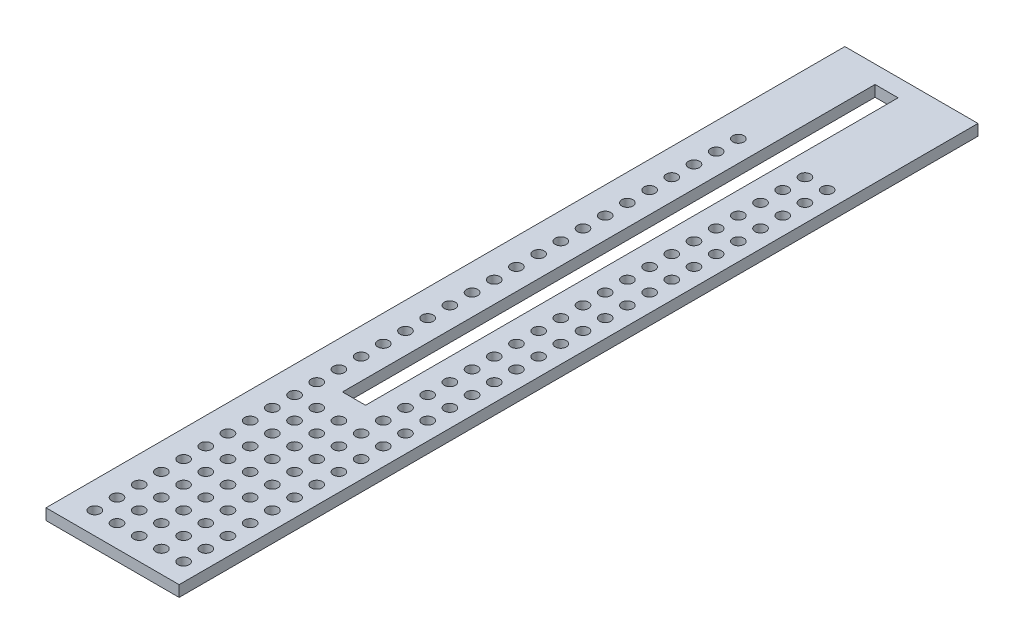
SolidWorks part; units mm, degrees
ref_plane "Front Plane" through (0, 0, 0) normal (0, 0, 1) x (1, 0, 0)
ref_plane "Top Plane" through (0, 0, 0) normal (0, 1, 0) x (1, 0, 0)
ref_plane "Right Plane" through (0, 0, 0) normal (1, 0, 0) x (0, 0, -1)
sketch "Sketch1" plane through (0, 0, 0) normal (0, 0, 1) x (1, 0, 0)
  line L0 (1.5875, 47.625) -> (36.5125, 47.625)
  line L1 (1.5875, -50.8) -> (-1.5875, -50.8)
  line L2 (1.5875, -50.8) -> (1.5875, 47.625)
  line L4 (-1.5875, -50.8) -> (-1.5875, 50.8)
  line L5 (1.5875, -50.8) -> (-1.5875, 50.8) construction
  line L6 (3.5127, 112.4075) -> (-1.5875, -50.8) construction
  line L7 (-1.5875, 50.8) -> (36.5125, 50.8)
  line L10 (36.5125, 50.8) -> (36.5125, 47.625)
  point P0 (0, 0)
  point P7 (0, -50.8)
  dimension "D1" = 3.175
  dimension "D2" = 3.175
  dimension "D3" = 38.1
  dimension "D4" = 101.6
extrude "Boss-Extrude1" add sketch "Sketch1" along normal blind 228.6
sketch "Sketch2" plane through (1.5875, 0, 0) normal (1, 0, 0) x (0, 0, -1)
  line L0 (-228.6, -29.4596) -> (0, 47.625) construction
  line L1 (-228.6, -50.8) -> (-228.6, 47.625) construction
  line L2 (-228.6, 47.625) -> (0, 47.625) construction
  line L3 (0, -50.8) -> (0, 47.625) construction
ref_plane "Plane1 - BACKBOARD PLANE" through (0, 42.7626, 14.4197) normal (0, -0.9476, -0.3195) x (0, 0.3195, -0.9476)
ref_plane "Plane1" through (0, -1.5875, 0) normal (0, -1, 0) x (-1, 0, 0)
sketch "Sketch3" plane through (-1.5875, 0, 0) normal (-1, 0, 0) x (0, 0, 1)
  line L0 (228.6, -50.8) -> (0, -50.8) construction
  line L1 (82.55, -32.385) -> (6.35, -32.385)
  line L2 (82.55, -32.385) -> (82.55, -38.735)
  line L3 (82.55, -38.735) -> (6.35, -38.735)
  line L4 (6.35, -32.385) -> (6.35, -38.735)
  line L5 (82.55, -32.385) -> (6.35, -38.735) construction
  line L6 (82.55, -38.735) -> (6.35, -32.385) construction
  line L7 (0, 50.8) -> (0, -50.8) construction
  line L18 (6.35, 33.1888) -> (82.55, 33.1888)
  line L19 (6.35, 33.1888) -> (6.35, 26.2472)
  line L20 (6.35, 26.2472) -> (82.55, 26.2472)
  line L21 (82.55, 33.1888) -> (82.55, 26.2472)
  point P0 (44.45, -35.56)
  point P13 (6.35, 29.718)
  point P14 (6.35, -35.56)
  dimension "D1" = 6.35
  dimension "D2" = 15.24
  dimension "D3" = 76.2
  dimension "D4" = 6.35
  dimension "D5" = 65.278
extrude "Cut-Extrude1" cut sketch "Sketch3" against normal up to next
sketch "Sketch4" plane through (-1.5875, 0, 0) normal (-1, 0, 0) x (0, 0, 1)
  circle A0 centre (103.8185, 40.3289) radius 1.5875
  circle A1 centre (110.1685, 40.3289) radius 1.5875
  circle A2 centre (116.5185, 40.3289) radius 1.5875
  circle A3 centre (122.8685, 40.3289) radius 1.5875
  circle A4 centre (129.2185, 40.3289) radius 1.5875
  circle A5 centre (110.1685, 33.9789) radius 1.5875
  circle A6 centre (116.5185, 33.9789) radius 1.5875
  circle A7 centre (122.8685, 33.9789) radius 1.5875
  circle A8 centre (129.2185, 33.9789) radius 1.5875
  circle A9 centre (110.1685, 27.6289) radius 1.5875
  circle A10 centre (116.5185, 27.6289) radius 1.5875
  circle A11 centre (122.8685, 27.6289) radius 1.5875
  circle A12 centre (129.2185, 27.6289) radius 1.5875
  circle A13 centre (110.1685, 21.2789) radius 1.5875
  circle A14 centre (116.5185, 21.2789) radius 1.5875
  circle A15 centre (122.8685, 21.2789) radius 1.5875
  circle A16 centre (129.2185, 21.2789) radius 1.5875
  circle A17 centre (103.8185, 33.9789) radius 1.5875
  circle A18 centre (103.8185, 27.6289) radius 1.5875
  circle A19 centre (103.8185, 21.2789) radius 1.5875
  circle A20 centre (135.5685, 40.3289) radius 1.5875
  circle A21 centre (141.9185, 40.3289) radius 1.5875
  circle A22 centre (148.2685, 40.3289) radius 1.5875
  circle A23 centre (154.6185, 40.3289) radius 1.5875
  circle A24 centre (160.9685, 40.3289) radius 1.5875
  circle A25 centre (167.3185, 40.3289) radius 1.5875
  circle A26 centre (173.6685, 40.3289) radius 1.5875
  circle A27 centre (180.0185, 40.3289) radius 1.5875
  circle A28 centre (186.3685, 40.3289) radius 1.5875
  circle A29 centre (192.7185, 40.3289) radius 1.5875
  circle A30 centre (199.0685, 40.3289) radius 1.5875
  circle A31 centre (205.4185, 40.3289) radius 1.5875
  circle A32 centre (211.7685, 40.3289) radius 1.5875
  circle A33 centre (218.1185, 40.3289) radius 1.5875
  circle A34 centre (135.5685, 33.9789) radius 1.5875
  circle A35 centre (141.9185, 33.9789) radius 1.5875
  circle A36 centre (148.2685, 33.9789) radius 1.5875
  circle A37 centre (154.6185, 33.9789) radius 1.5875
  circle A38 centre (160.9685, 33.9789) radius 1.5875
  circle A39 centre (167.3185, 33.9789) radius 1.5875
  circle A40 centre (173.6685, 33.9789) radius 1.5875
  circle A41 centre (180.0185, 33.9789) radius 1.5875
  circle A42 centre (186.3685, 33.9789) radius 1.5875
  circle A43 centre (192.7185, 33.9789) radius 1.5875
  circle A44 centre (199.0685, 33.9789) radius 1.5875
  circle A45 centre (205.4185, 33.9789) radius 1.5875
  circle A46 centre (211.7685, 33.9789) radius 1.5875
  circle A47 centre (218.1185, 33.9789) radius 1.5875
  circle A48 centre (135.5685, 27.6289) radius 1.5875
  circle A49 centre (141.9185, 27.6289) radius 1.5875
  circle A50 centre (148.2685, 27.6289) radius 1.5875
  circle A51 centre (154.6185, 27.6289) radius 1.5875
  circle A52 centre (160.9685, 27.6289) radius 1.5875
  circle A53 centre (167.3185, 27.6289) radius 1.5875
  circle A54 centre (173.6685, 27.6289) radius 1.5875
  circle A55 centre (180.0185, 27.6289) radius 1.5875
  circle A56 centre (186.3685, 27.6289) radius 1.5875
  circle A57 centre (192.7185, 27.6289) radius 1.5875
  circle A58 centre (199.0685, 27.6289) radius 1.5875
  circle A59 centre (205.4185, 27.6289) radius 1.5875
  circle A60 centre (211.7685, 27.6289) radius 1.5875
  circle A61 centre (218.1185, 27.6289) radius 1.5875
  circle A62 centre (135.5685, 21.2789) radius 1.5875
  circle A63 centre (141.9185, 21.2789) radius 1.5875
  circle A64 centre (148.2685, 21.2789) radius 1.5875
  circle A65 centre (154.6185, 21.2789) radius 1.5875
  circle A66 centre (160.9685, 21.2789) radius 1.5875
  circle A67 centre (167.3185, 21.2789) radius 1.5875
  circle A68 centre (173.6685, 21.2789) radius 1.5875
  circle A69 centre (180.0185, 21.2789) radius 1.5875
  circle A70 centre (186.3685, 21.2789) radius 1.5875
  circle A71 centre (192.7185, 21.2789) radius 1.5875
  circle A72 centre (199.0685, 21.2789) radius 1.5875
  circle A73 centre (205.4185, 21.2789) radius 1.5875
  circle A74 centre (211.7685, 21.2789) radius 1.5875
  circle A75 centre (218.1185, 21.2789) radius 1.5875
  circle A76 centre (103.8185, 14.9289) radius 1.5875
  circle A77 centre (110.1685, 14.9289) radius 1.5875
  circle A78 centre (116.5185, 14.9289) radius 1.5875
  circle A79 centre (122.8685, 14.9289) radius 1.5875
  circle A80 centre (129.2185, 14.9289) radius 1.5875
  circle A81 centre (135.5685, 14.9289) radius 1.5875
  circle A82 centre (141.9185, 14.9289) radius 1.5875
  circle A83 centre (148.2685, 14.9289) radius 1.5875
  circle A84 centre (154.6185, 14.9289) radius 1.5875
  circle A85 centre (160.9685, 14.9289) radius 1.5875
  circle A86 centre (167.3185, 14.9289) radius 1.5875
  circle A87 centre (173.6685, 14.9289) radius 1.5875
  circle A88 centre (180.0185, 14.9289) radius 1.5875
  circle A89 centre (186.3685, 14.9289) radius 1.5875
  circle A90 centre (192.7185, 14.9289) radius 1.5875
  circle A91 centre (199.0685, 14.9289) radius 1.5875
  circle A92 centre (205.4185, 14.9289) radius 1.5875
  circle A93 centre (211.7685, 14.9289) radius 1.5875
  circle A94 centre (218.1185, 14.9289) radius 1.5875
  circle A95 centre (103.8185, 8.5789) radius 1.5875
  circle A96 centre (110.1685, 8.5789) radius 1.5875
  circle A97 centre (116.5185, 8.5789) radius 1.5875
  circle A98 centre (122.8685, 8.5789) radius 1.5875
  circle A99 centre (129.2185, 8.5789) radius 1.5875
  circle A100 centre (135.5685, 8.5789) radius 1.5875
  circle A101 centre (141.9185, 8.5789) radius 1.5875
  circle A102 centre (148.2685, 8.5789) radius 1.5875
  circle A103 centre (154.6185, 8.5789) radius 1.5875
  circle A104 centre (160.9685, 8.5789) radius 1.5875
  circle A105 centre (167.3185, 8.5789) radius 1.5875
  circle A106 centre (173.6685, 8.5789) radius 1.5875
  circle A107 centre (180.0185, 8.5789) radius 1.5875
  circle A108 centre (186.3685, 8.5789) radius 1.5875
  circle A109 centre (192.7185, 8.5789) radius 1.5875
  circle A110 centre (199.0685, 8.5789) radius 1.5875
  circle A111 centre (205.4185, 8.5789) radius 1.5875
  circle A112 centre (211.7685, 8.5789) radius 1.5875
  circle A113 centre (218.1185, 8.5789) radius 1.5875
  circle A114 centre (103.8185, 2.2289) radius 1.5875
  circle A115 centre (110.1685, 2.2289) radius 1.5875
  circle A116 centre (116.5185, 2.2289) radius 1.5875
  circle A117 centre (122.8685, 2.2289) radius 1.5875
  circle A118 centre (129.2185, 2.2289) radius 1.5875
  circle A119 centre (135.5685, 2.2289) radius 1.5875
  circle A120 centre (141.9185, 2.2289) radius 1.5875
  circle A121 centre (148.2685, 2.2289) radius 1.5875
  circle A122 centre (154.6185, 2.2289) radius 1.5875
  circle A123 centre (160.9685, 2.2289) radius 1.5875
  circle A124 centre (167.3185, 2.2289) radius 1.5875
  circle A125 centre (173.6685, 2.2289) radius 1.5875
  circle A126 centre (180.0185, 2.2289) radius 1.5875
  circle A127 centre (186.3685, 2.2289) radius 1.5875
  circle A128 centre (192.7185, 2.2289) radius 1.5875
  circle A129 centre (199.0685, 2.2289) radius 1.5875
  circle A130 centre (205.4185, 2.2289) radius 1.5875
  circle A131 centre (211.7685, 2.2289) radius 1.5875
  circle A132 centre (218.1185, 2.2289) radius 1.5875
  circle A133 centre (103.8185, -4.1211) radius 1.5875
  circle A134 centre (110.1685, -4.1211) radius 1.5875
  circle A135 centre (116.5185, -4.1211) radius 1.5875
  circle A136 centre (122.8685, -4.1211) radius 1.5875
  circle A137 centre (129.2185, -4.1211) radius 1.5875
  circle A138 centre (135.5685, -4.1211) radius 1.5875
  circle A139 centre (141.9185, -4.1211) radius 1.5875
  circle A140 centre (148.2685, -4.1211) radius 1.5875
  circle A141 centre (154.6185, -4.1211) radius 1.5875
  circle A142 centre (160.9685, -4.1211) radius 1.5875
  circle A143 centre (167.3185, -4.1211) radius 1.5875
  circle A144 centre (173.6685, -4.1211) radius 1.5875
  circle A145 centre (180.0185, -4.1211) radius 1.5875
  circle A146 centre (186.3685, -4.1211) radius 1.5875
  circle A147 centre (192.7185, -4.1211) radius 1.5875
  circle A148 centre (199.0685, -4.1211) radius 1.5875
  circle A149 centre (205.4185, -4.1211) radius 1.5875
  circle A150 centre (211.7685, -4.1211) radius 1.5875
  circle A151 centre (218.1185, -4.1211) radius 1.5875
  circle A152 centre (103.8185, -10.4711) radius 1.5875
  circle A153 centre (110.1685, -10.4711) radius 1.5875
  circle A154 centre (116.5185, -10.4711) radius 1.5875
  circle A155 centre (122.8685, -10.4711) radius 1.5875
  circle A156 centre (129.2185, -10.4711) radius 1.5875
  circle A157 centre (135.5685, -10.4711) radius 1.5875
  circle A158 centre (141.9185, -10.4711) radius 1.5875
  circle A159 centre (148.2685, -10.4711) radius 1.5875
  circle A160 centre (154.6185, -10.4711) radius 1.5875
  circle A161 centre (160.9685, -10.4711) radius 1.5875
  circle A162 centre (167.3185, -10.4711) radius 1.5875
  circle A163 centre (173.6685, -10.4711) radius 1.5875
  circle A164 centre (180.0185, -10.4711) radius 1.5875
  circle A165 centre (186.3685, -10.4711) radius 1.5875
  circle A166 centre (192.7185, -10.4711) radius 1.5875
  circle A167 centre (199.0685, -10.4711) radius 1.5875
  circle A168 centre (205.4185, -10.4711) radius 1.5875
  circle A169 centre (211.7685, -10.4711) radius 1.5875
  circle A170 centre (218.1185, -10.4711) radius 1.5875
  circle A171 centre (103.8185, -16.8211) radius 1.5875
  circle A172 centre (110.1685, -16.8211) radius 1.5875
  circle A173 centre (116.5185, -16.8211) radius 1.5875
  circle A174 centre (122.8685, -16.8211) radius 1.5875
  circle A175 centre (129.2185, -16.8211) radius 1.5875
  circle A176 centre (135.5685, -16.8211) radius 1.5875
  circle A177 centre (141.9185, -16.8211) radius 1.5875
  circle A178 centre (148.2685, -16.8211) radius 1.5875
  circle A179 centre (154.6185, -16.8211) radius 1.5875
  circle A180 centre (160.9685, -16.8211) radius 1.5875
  circle A181 centre (167.3185, -16.8211) radius 1.5875
  circle A182 centre (173.6685, -16.8211) radius 1.5875
  circle A183 centre (180.0185, -16.8211) radius 1.5875
  circle A184 centre (186.3685, -16.8211) radius 1.5875
  circle A185 centre (192.7185, -16.8211) radius 1.5875
  circle A186 centre (199.0685, -16.8211) radius 1.5875
  circle A187 centre (205.4185, -16.8211) radius 1.5875
  circle A188 centre (211.7685, -16.8211) radius 1.5875
  circle A189 centre (218.1185, -16.8211) radius 1.5875
  circle A190 centre (103.8185, -23.1711) radius 1.5875
  circle A191 centre (110.1685, -23.1711) radius 1.5875
  circle A192 centre (116.5185, -23.1711) radius 1.5875
  circle A193 centre (122.8685, -23.1711) radius 1.5875
  circle A194 centre (129.2185, -23.1711) radius 1.5875
  circle A195 centre (135.5685, -23.1711) radius 1.5875
  circle A196 centre (141.9185, -23.1711) radius 1.5875
  circle A197 centre (148.2685, -23.1711) radius 1.5875
  circle A198 centre (154.6185, -23.1711) radius 1.5875
  circle A199 centre (160.9685, -23.1711) radius 1.5875
  circle A200 centre (167.3185, -23.1711) radius 1.5875
  circle A201 centre (173.6685, -23.1711) radius 1.5875
  circle A202 centre (180.0185, -23.1711) radius 1.5875
  circle A203 centre (186.3685, -23.1711) radius 1.5875
  circle A204 centre (192.7185, -23.1711) radius 1.5875
  circle A205 centre (199.0685, -23.1711) radius 1.5875
  circle A206 centre (205.4185, -23.1711) radius 1.5875
  circle A207 centre (211.7685, -23.1711) radius 1.5875
  circle A208 centre (218.1185, -23.1711) radius 1.5875
  circle A209 centre (103.8185, -29.5211) radius 1.5875
  circle A210 centre (110.1685, -29.5211) radius 1.5875
  circle A211 centre (116.5185, -29.5211) radius 1.5875
  circle A212 centre (122.8685, -29.5211) radius 1.5875
  circle A213 centre (129.2185, -29.5211) radius 1.5875
  circle A214 centre (135.5685, -29.5211) radius 1.5875
  circle A215 centre (141.9185, -29.5211) radius 1.5875
  circle A216 centre (148.2685, -29.5211) radius 1.5875
  circle A217 centre (154.6185, -29.5211) radius 1.5875
  circle A218 centre (160.9685, -29.5211) radius 1.5875
  circle A219 centre (167.3185, -29.5211) radius 1.5875
  circle A220 centre (173.6685, -29.5211) radius 1.5875
  circle A221 centre (180.0185, -29.5211) radius 1.5875
  circle A222 centre (186.3685, -29.5211) radius 1.5875
  circle A223 centre (192.7185, -29.5211) radius 1.5875
  circle A224 centre (199.0685, -29.5211) radius 1.5875
  circle A225 centre (205.4185, -29.5211) radius 1.5875
  circle A226 centre (211.7685, -29.5211) radius 1.5875
  circle A227 centre (218.1185, -29.5211) radius 1.5875
  circle A228 centre (103.8185, -35.8711) radius 1.5875
  circle A229 centre (110.1685, -35.8711) radius 1.5875
  circle A230 centre (116.5185, -35.8711) radius 1.5875
  circle A231 centre (122.8685, -35.8711) radius 1.5875
  circle A232 centre (129.2185, -35.8711) radius 1.5875
  circle A233 centre (135.5685, -35.8711) radius 1.5875
  circle A234 centre (141.9185, -35.8711) radius 1.5875
  circle A235 centre (148.2685, -35.8711) radius 1.5875
  circle A236 centre (154.6185, -35.8711) radius 1.5875
  circle A237 centre (160.9685, -35.8711) radius 1.5875
  circle A238 centre (167.3185, -35.8711) radius 1.5875
  circle A239 centre (173.6685, -35.8711) radius 1.5875
  circle A240 centre (180.0185, -35.8711) radius 1.5875
  circle A241 centre (186.3685, -35.8711) radius 1.5875
  circle A242 centre (192.7185, -35.8711) radius 1.5875
  circle A243 centre (199.0685, -35.8711) radius 1.5875
  circle A244 centre (205.4185, -35.8711) radius 1.5875
  circle A245 centre (211.7685, -35.8711) radius 1.5875
  circle A246 centre (218.1185, -35.8711) radius 1.5875
  circle A247 centre (103.8185, -42.2211) radius 1.5875
  circle A248 centre (110.1685, -42.2211) radius 1.5875
  circle A249 centre (116.5185, -42.2211) radius 1.5875
  circle A250 centre (122.8685, -42.2211) radius 1.5875
  circle A251 centre (129.2185, -42.2211) radius 1.5875
  circle A252 centre (135.5685, -42.2211) radius 1.5875
  circle A253 centre (141.9185, -42.2211) radius 1.5875
  circle A254 centre (148.2685, -42.2211) radius 1.5875
  circle A255 centre (154.6185, -42.2211) radius 1.5875
  circle A256 centre (160.9685, -42.2211) radius 1.5875
  circle A257 centre (167.3185, -42.2211) radius 1.5875
  circle A258 centre (173.6685, -42.2211) radius 1.5875
  circle A259 centre (180.0185, -42.2211) radius 1.5875
  circle A260 centre (186.3685, -42.2211) radius 1.5875
  circle A261 centre (192.7185, -42.2211) radius 1.5875
  circle A262 centre (199.0685, -42.2211) radius 1.5875
  circle A263 centre (205.4185, -42.2211) radius 1.5875
  circle A264 centre (211.7685, -42.2211) radius 1.5875
  circle A265 centre (218.1185, -42.2211) radius 1.5875
  dimension "D1" = 3.175
  dimension "D2" = 19
  dimension "D3" = 14
extrude "Cut-Extrude2" cut sketch "Sketch4" against normal up to next (3.175 mm away)
sketch "Sketch5" plane through (0, 50.8, 0) normal (0, 1, 0) x (1, 0, 0)
  line L0 (36.5125, 0) -> (-1.5875, 0) construction
  line L1 (18.7325, -5.08) -> (12.1285, -5.08)
  line L2 (18.7325, -5.08) -> (18.7325, -157.48)
  line L3 (18.7325, -157.48) -> (12.1285, -157.48)
  line L4 (12.1285, -5.08) -> (12.1285, -157.48)
  line L5 (36.5125, -228.6) -> (36.5125, 0) construction
  point P8 (15.4305, -5.08)
  dimension "D1" = 6.604
  dimension "D2" = 152.4
  dimension "D3" = 5.08
  dimension "D4" = 21.082
extrude "Cut-Extrude3" cut sketch "Sketch5" against normal up to next
sketch "Sketch6" plane through (0, 50.8, 0) normal (0, 1, 0) x (1, 0, 0)
  line L0 (36.5125, -228.6) -> (-1.5875, -228.6) construction
  line L1 (36.5125, -228.6) -> (36.5125, 0) construction
  circle A0 centre (6.0325, -222.25) radius 1.5875
  circle A1 centre (12.3825, -222.25) radius 1.5875
  circle A2 centre (18.7325, -222.25) radius 1.5875
  circle A3 centre (25.0825, -222.25) radius 1.5875
  circle A4 centre (31.4325, -222.25) radius 1.5875
  circle A5 centre (12.3825, -215.9) radius 1.5875
  circle A6 centre (18.7325, -215.9) radius 1.5875
  circle A7 centre (25.0825, -215.9) radius 1.5875
  circle A8 centre (31.4325, -215.9) radius 1.5875
  circle A9 centre (12.3825, -209.55) radius 1.5875
  circle A10 centre (18.7325, -209.55) radius 1.5875
  circle A11 centre (25.0825, -209.55) radius 1.5875
  circle A12 centre (31.4325, -209.55) radius 1.5875
  circle A13 centre (12.3825, -203.2) radius 1.5875
  circle A14 centre (18.7325, -203.2) radius 1.5875
  circle A15 centre (25.0825, -203.2) radius 1.5875
  circle A16 centre (31.4325, -203.2) radius 1.5875
  circle A17 centre (12.3825, -196.85) radius 1.5875
  circle A18 centre (18.7325, -196.85) radius 1.5875
  circle A19 centre (25.0825, -196.85) radius 1.5875
  circle A20 centre (31.4325, -196.85) radius 1.5875
  circle A21 centre (12.3825, -190.5) radius 1.5875
  circle A22 centre (18.7325, -190.5) radius 1.5875
  circle A23 centre (25.0825, -190.5) radius 1.5875
  circle A24 centre (31.4325, -190.5) radius 1.5875
  circle A25 centre (12.3825, -184.15) radius 1.5875
  circle A26 centre (18.7325, -184.15) radius 1.5875
  circle A27 centre (25.0825, -184.15) radius 1.5875
  circle A28 centre (31.4325, -184.15) radius 1.5875
  circle A29 centre (12.3825, -177.8) radius 1.5875
  circle A30 centre (18.7325, -177.8) radius 1.5875
  circle A31 centre (25.0825, -177.8) radius 1.5875
  circle A32 centre (31.4325, -177.8) radius 1.5875
  circle A33 centre (12.3825, -171.45) radius 1.5875
  circle A34 centre (18.7325, -171.45) radius 1.5875
  circle A35 centre (25.0825, -171.45) radius 1.5875
  circle A36 centre (31.4325, -171.45) radius 1.5875
  circle A37 centre (12.3825, -165.1) radius 1.5875
  circle A38 centre (18.7325, -165.1) radius 1.5875
  circle A39 centre (25.0825, -165.1) radius 1.5875
  circle A40 centre (31.4325, -165.1) radius 1.5875
  circle A43 centre (25.0825, -158.75) radius 1.5875
  circle A44 centre (31.4325, -158.75) radius 1.5875
  circle A47 centre (25.0825, -152.4) radius 1.5875
  circle A48 centre (31.4325, -152.4) radius 1.5875
  circle A51 centre (25.0825, -146.05) radius 1.5875
  circle A52 centre (31.4325, -146.05) radius 1.5875
  circle A55 centre (25.0825, -139.7) radius 1.5875
  circle A56 centre (31.4325, -139.7) radius 1.5875
  circle A59 centre (25.0825, -133.35) radius 1.5875
  circle A60 centre (31.4325, -133.35) radius 1.5875
  circle A63 centre (25.0825, -127) radius 1.5875
  circle A64 centre (31.4325, -127) radius 1.5875
  circle A67 centre (25.0825, -120.65) radius 1.5875
  circle A68 centre (31.4325, -120.65) radius 1.5875
  circle A71 centre (25.0825, -114.3) radius 1.5875
  circle A72 centre (31.4325, -114.3) radius 1.5875
  circle A75 centre (25.0825, -107.95) radius 1.5875
  circle A76 centre (31.4325, -107.95) radius 1.5875
  circle A79 centre (25.0825, -101.6) radius 1.5875
  circle A80 centre (31.4325, -101.6) radius 1.5875
  circle A83 centre (25.0825, -95.25) radius 1.5875
  circle A84 centre (31.4325, -95.25) radius 1.5875
  circle A87 centre (25.0825, -88.9) radius 1.5875
  circle A88 centre (31.4325, -88.9) radius 1.5875
  circle A91 centre (25.0825, -82.55) radius 1.5875
  circle A92 centre (31.4325, -82.55) radius 1.5875
  circle A95 centre (25.0825, -76.2) radius 1.5875
  circle A96 centre (31.4325, -76.2) radius 1.5875
  circle A99 centre (25.0825, -69.85) radius 1.5875
  circle A100 centre (31.4325, -69.85) radius 1.5875
  circle A103 centre (25.0825, -63.5) radius 1.5875
  circle A104 centre (31.4325, -63.5) radius 1.5875
  circle A107 centre (25.0825, -57.15) radius 1.5875
  circle A108 centre (31.4325, -57.15) radius 1.5875
  circle A111 centre (25.0825, -50.8) radius 1.5875
  circle A112 centre (31.4325, -50.8) radius 1.5875
  circle A115 centre (25.0825, -44.45) radius 1.5875
  circle A116 centre (31.4325, -44.45) radius 1.5875
  circle A119 centre (25.0825, -38.1) radius 1.5875
  circle A120 centre (31.4325, -38.1) radius 1.5875
  circle A121 centre (6.0325, -215.9) radius 1.5875
  circle A122 centre (6.0325, -209.55) radius 1.5875
  circle A123 centre (6.0325, -203.2) radius 1.5875
  circle A124 centre (6.0325, -196.85) radius 1.5875
  circle A125 centre (6.0325, -190.5) radius 1.5875
  circle A126 centre (6.0325, -184.15) radius 1.5875
  circle A127 centre (6.0325, -177.8) radius 1.5875
  circle A128 centre (6.0325, -171.45) radius 1.5875
  circle A129 centre (6.0325, -165.1) radius 1.5875
  circle A130 centre (6.0325, -158.75) radius 1.5875
  circle A131 centre (6.0325, -152.4) radius 1.5875
  circle A132 centre (6.0325, -146.05) radius 1.5875
  circle A133 centre (6.0325, -139.7) radius 1.5875
  circle A134 centre (6.0325, -133.35) radius 1.5875
  circle A135 centre (6.0325, -127) radius 1.5875
  circle A136 centre (6.0325, -120.65) radius 1.5875
  circle A137 centre (6.0325, -114.3) radius 1.5875
  circle A138 centre (6.0325, -107.95) radius 1.5875
  circle A139 centre (6.0325, -101.6) radius 1.5875
  circle A140 centre (6.0325, -95.25) radius 1.5875
  circle A141 centre (6.0325, -88.9) radius 1.5875
  circle A142 centre (6.0325, -82.55) radius 1.5875
  circle A143 centre (6.0325, -76.2) radius 1.5875
  circle A144 centre (6.0325, -69.85) radius 1.5875
  circle A145 centre (6.0325, -63.5) radius 1.5875
  circle A146 centre (6.0325, -57.15) radius 1.5875
  circle A147 centre (6.0325, -50.8) radius 1.5875
  circle A148 centre (6.0325, -44.45) radius 1.5875
  circle A149 centre (6.0325, -38.1) radius 1.5875
  circle A150 centre (18.7325, -50.8) radius 1.5875 [skipped]
  circle A151 centre (12.3825, -44.45) radius 1.5875 [skipped]
  circle A152 centre (18.7325, -44.45) radius 1.5875 [skipped]
  circle A153 centre (12.3825, -38.1) radius 1.5875 [skipped]
  circle A154 centre (18.7325, -38.1) radius 1.5875 [skipped]
  circle A155 centre (12.3825, -63.5) radius 1.5875 [skipped]
  circle A156 centre (18.7325, -63.5) radius 1.5875 [skipped]
  circle A157 centre (12.3825, -57.15) radius 1.5875 [skipped]
  circle A158 centre (18.7325, -57.15) radius 1.5875 [skipped]
  circle A159 centre (12.3825, -50.8) radius 1.5875 [skipped]
  circle A160 centre (12.3825, -158.75) radius 1.5875 [skipped]
  circle A161 centre (18.7325, -158.75) radius 1.5875 [skipped]
  circle A162 centre (12.3825, -152.4) radius 1.5875 [skipped]
  circle A163 centre (18.7325, -152.4) radius 1.5875 [skipped]
  circle A164 centre (12.3825, -146.05) radius 1.5875 [skipped]
  circle A165 centre (18.7325, -146.05) radius 1.5875 [skipped]
  circle A166 centre (12.3825, -139.7) radius 1.5875 [skipped]
  circle A167 centre (18.7325, -139.7) radius 1.5875 [skipped]
  circle A168 centre (12.3825, -133.35) radius 1.5875 [skipped]
  circle A169 centre (18.7325, -133.35) radius 1.5875 [skipped]
  circle A170 centre (12.3825, -127) radius 1.5875 [skipped]
  circle A171 centre (18.7325, -127) radius 1.5875 [skipped]
  circle A172 centre (12.3825, -120.65) radius 1.5875 [skipped]
  circle A173 centre (18.7325, -120.65) radius 1.5875 [skipped]
  circle A174 centre (12.3825, -114.3) radius 1.5875 [skipped]
  circle A175 centre (18.7325, -114.3) radius 1.5875 [skipped]
  circle A176 centre (12.3825, -107.95) radius 1.5875 [skipped]
  circle A177 centre (18.7325, -107.95) radius 1.5875 [skipped]
  circle A178 centre (12.3825, -101.6) radius 1.5875 [skipped]
  circle A179 centre (18.7325, -101.6) radius 1.5875 [skipped]
  circle A180 centre (12.3825, -95.25) radius 1.5875 [skipped]
  circle A181 centre (18.7325, -95.25) radius 1.5875 [skipped]
  circle A182 centre (12.3825, -88.9) radius 1.5875 [skipped]
  circle A183 centre (18.7325, -88.9) radius 1.5875 [skipped]
  circle A184 centre (12.3825, -82.55) radius 1.5875 [skipped]
  circle A185 centre (18.7325, -82.55) radius 1.5875 [skipped]
  circle A186 centre (12.3825, -76.2) radius 1.5875 [skipped]
  circle A187 centre (18.7325, -76.2) radius 1.5875 [skipped]
  circle A188 centre (12.3825, -69.85) radius 1.5875 [skipped]
  circle A189 centre (18.7325, -69.85) radius 1.5875 [skipped]
  dimension "D1" = 3.175
  dimension "D2" = 6.35
  dimension "D3" = 30.48
  dimension "D4" = 5
  dimension "D5" = 30
extrude "Cut-Extrude4" cut sketch "Sketch6" against normal up to next (3.175 mm away)
ref_plane "Plane2" through (1.5875, 0, 0) normal (1, 0, 0) x (0, 0, -1)
sketch "Sketch7" plane through (-1.5875, 0, 0) normal (-1, 0, 0) x (0, 0, 1)
  line L1 (228.6, -50.8) -> (0, -50.8)
  line L2 (228.6, -50.8) -> (228.6, 47.625)
  line L3 (228.6, 47.625) -> (0, 47.625)
  line L4 (0, -50.8) -> (0, 47.625)
extrude "Cut-Extrude5" cut sketch "Sketch7" against normal up to next
equation "\"eighthinch\"= 0.125"
equation "\"D2@Sketch1\"=\"eighthinch\""
